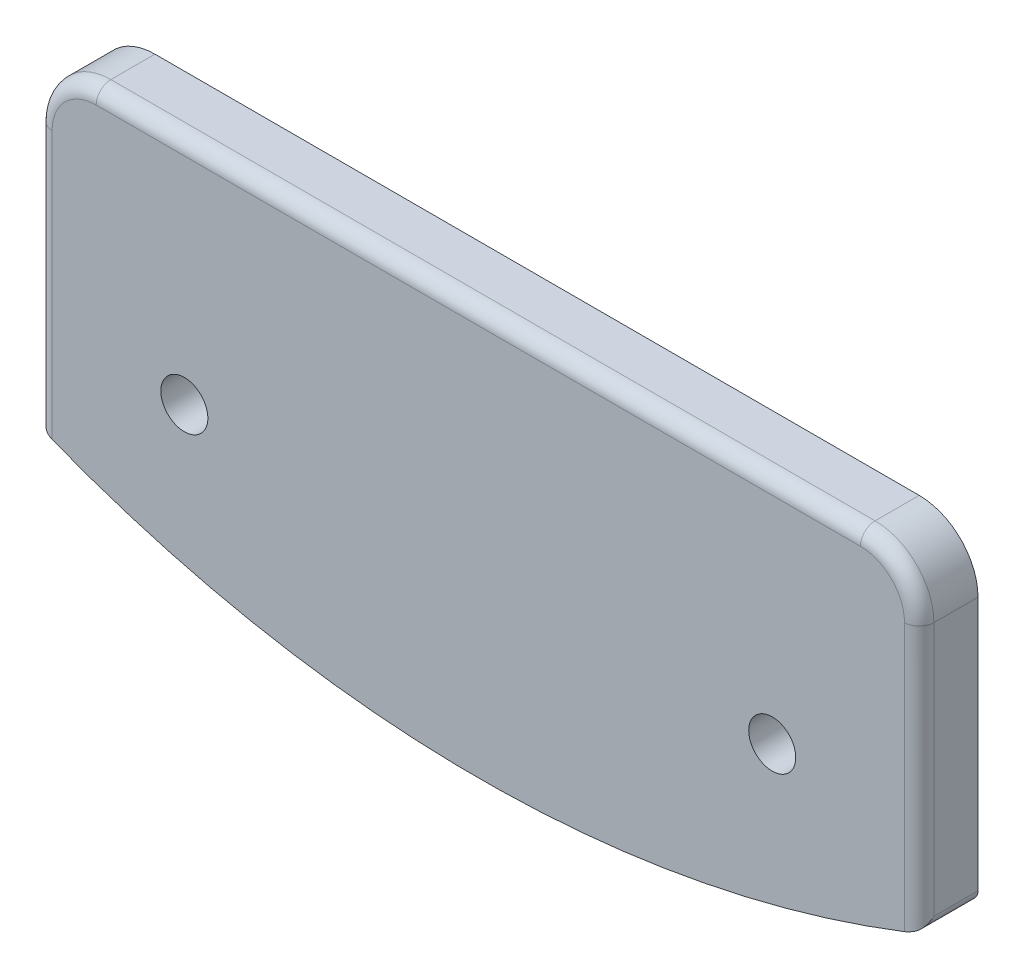
SolidWorks part; units mm, degrees
ref_plane "Спереди" through (0, 0, 0) normal (0, 0, 1) x (1, 0, 0)
ref_plane "Сверху" through (0, 0, 0) normal (0, 1, 0) x (1, 0, 0)
ref_plane "Справа" through (0, 0, 0) normal (1, 0, 0) x (0, 0, -1)
sketch "Эскиз1" plane through (0, 0, 0) normal (0, 0, 1) x (1, 0, 0)
  line L0 (0, -1.246) -> (0, -50001.246) construction
  line L1 (-26, -52.35) -> (26, -52.35)
  line L2 (-26, -53.35) -> (2.65, -53.35)
  line L3 (-29, -56.35) -> (-29, -64)
  line L4 (-29, -64) -> (5.65, -64)
  line L5 (5.65, -56.35) -> (5.65, -64)
  line L7 (-30, -56.35) -> (-30, -74.162)
  line L10 (30, -56.35) -> (30, -74.162)
  arc A1 (-26, -53.35) -> (-29, -56.35) centre (-26, -56.35) ccw
  arc A2 (5.65, -56.35) -> (2.65, -53.35) centre (2.65, -56.35) ccw
  arc A3 (-59.4802, -53.4986) -> (59.4802, -53.4986) centre (0, 0) ccw construction
  arc A4 (-30, -74.162) -> (30, -74.162) centre (0, 0) ccw
  circle A5 centre (-20, -68) radius 1.6
  circle A6 centre (20, -68) radius 1.6
  circle A7 centre (-22.55, -54.35) radius 0.5 construction
  circle A8 centre (4.65, -62.45) radius 0.5 construction
  arc A9 (-30, -56.35) -> (-26, -52.35) centre (-26, -56.35) cw
  arc A11 (30, -56.35) -> (26, -52.35) centre (26, -56.35) ccw
  point P3 (-20, -68)
  point P9 (20, -68)
  point P16 (0, 0)
  point P18 (6.0046, -51.85)
  point P19 (6.0046, -52.6662)
  point P31 (5.65, -52.5818)
  point P38 (29.7143, -73.9578)
  point P40 (0, 0)
  point P47 (25.342, -51.85)
  dimension "D1" = 3.2
  dimension "D4" = 0.5
  dimension "D6" = 0.5
  dimension "D8" = 3
  dimension "D3" = 0.5
  dimension "D5" = 0.5
  dimension "D7" = 1
extrude "Бобышка-Вытянуть1" add sketch "Эскиз1" along normal blind 2.5
extrude "Бобышка-Вытянуть2" add sketch "Эскиз1<2>" along normal blind 1.5 from surface contours A4 L10 A11 L1 A9 L7 | A5 | A6 starting at face at (18.4, -68, 2.5)
sketch "Эскиз1<2>" plane through (0, 0, 0) normal (0, 0, 1) x (1, 0, 0) same geometry as "Эскиз1"
fillet "Скругление1" radius 1 2 edges at (-29, -64, 1.25) (5.65, -64, 1.25)
fillet "Скругление2" radius 1 5 edges at (-30, -65.256, 4) (-28.8284, -53.5216, 4) (0, -52.35, 4) (28.8284, -53.5216, 4) (30, -65.256, 4)
fillet "Скругление3" radius 0.75 2 edges at (-30, -74.162, 1.5) (30, -74.162, 1.5) tangent propagation no
